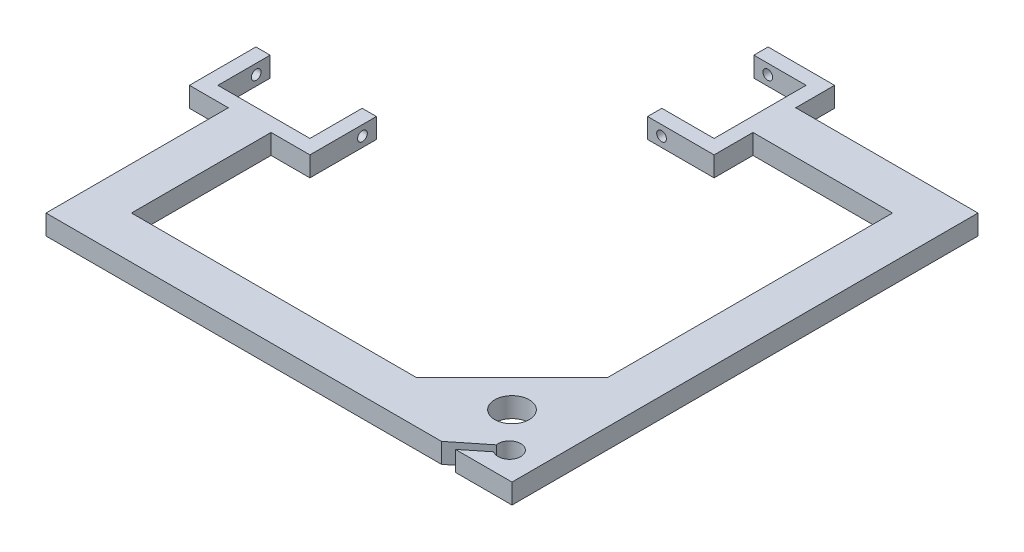
SolidWorks part; units mm, degrees
ref_plane "Front Plane" through (0, 0, 0) normal (0, 0, 1) x (1, 0, 0)
ref_plane "Top Plane" through (0, 0, 0) normal (0, 1, 0) x (1, 0, 0)
ref_plane "Right Plane" through (0, 0, 0) normal (1, 0, 0) x (0, 0, -1)
sketch "Sketch1" plane through (0, 0, 0) normal (0, 1, 0) x (1, 0, 0)
  line L0 (-84.9, -24.6552) -> (-84.9, -42.9952)
  line L1 (-84.9, -42.9952) -> (-52.6, -42.9952)
  line L2 (-52.6, -42.9952) -> (-52.6, -24.6552)
  line L3 (-52.6, -24.6552) -> (-47.6, -24.6552)
  line L4 (-47.6, -24.6552) -> (-47.6, -47.9952)
  line L5 (-47.6, -47.9952) -> (-61.25, -47.9952)
  line L6 (-84.9, -24.6552) -> (-89.9, -24.6552)
  line L7 (-89.9, -24.6552) -> (-89.9, -47.9952)
  line L8 (-89.9, -47.9952) -> (-76.25, -47.9952)
  line L9 (-76.25, -47.9952) -> (-76.25, -111.9952)
  line L10 (-61.25, -47.9952) -> (-61.25, -96.9952)
  line L11 (-76.25, -111.9952) -> (38.75, -111.9952)
  line L12 (-61.25, -96.9952) -> (38.75, -96.9952)
  line L14 (23.34, 36.5948) -> (23.34, 22.9448)
  line L15 (23.34, 22.9448) -> (0, 22.9448)
  line L16 (0, 22.9448) -> (0, 27.9448)
  line L17 (0, 27.9448) -> (18.34, 27.9448)
  line L18 (18.34, 27.9448) -> (18.34, 60.2448)
  line L19 (18.34, 60.2448) -> (0, 60.2448)
  line L20 (0, 60.2448) -> (0, 65.2448)
  line L21 (0, 65.2448) -> (23.34, 65.2448)
  line L22 (23.34, 65.2448) -> (23.34, 51.5948)
  line L28 (23.34, 36.5948) -> (72.34, 36.5948)
  line L29 (72.34, 36.5948) -> (72.34, -63.4052)
  line L30 (23.34, 51.5948) -> (87.34, 51.5948)
  line L31 (87.34, 51.5948) -> (87.34, -63.4052)
  line L32 (72.34, -63.4052) -> (38.75, -96.9952)
  line L34 (87.34, -111.9952) -> (87.34, -63.4052)
  line L35 (73.2655, -103.434) -> (62.5726, -111.9952)
  line L36 (67.475, -111.9952) -> (74.9461, -106.0135)
  line L37 (67.475, -111.9952) -> (87.34, -111.9952)
  line L38 (62.5726, -111.9952) -> (38.75, -111.9952)
  circle A2 centre (65.34, -89.9952) radius 6.05
  arc A3 (74.9461, -106.0135) -> (73.2655, -103.434) centre (77.17, -102.7275) ccw
  dimension "D11" = 7
  dimension "D12" = 7
  dimension "D13" = 12.1
  dimension "D1" = 5
  dimension "D2" = 18.34
  dimension "D3" = 5
  dimension "D4" = 32.3
  dimension "D5" = 100
  dimension "D6" = 15
  dimension "D7" = 49
  dimension "D8" = 15
  dimension "D9" = 70.94
  dimension "D10" = 70.94
  dimension "D14" = 4.9023
extrude "Boss-Extrude1" add sketch "Sketch1" along normal blind 7
sketch "Sketch2" plane through (0, 0, -22.9448) normal (0, 0, 1) x (1, 0, 0)
  line L0 (0, 7) -> (0, 0) construction
  line L1 (0, 7) -> (23.34, 7) construction
  line L3 (0, 0) -> (23.34, 0) construction
  circle A0 centre (4.9, 3.5) radius 1.7
  dimension "D1" = 3.4
  dimension "D2" = 4.9
  dimension "D3" = 3.5
  dimension "D4" = 3.5
extrude "Cut-Extrude1" cut sketch "Sketch2" against normal blind 50
sketch "Sketch3" plane through (-47.6, 0, 0) normal (1, 0, 0) x (0, 0, -1)
  line L0 (-24.6552, 7) -> (-24.6552, 0) construction
  line L1 (-47.9952, 7) -> (-24.6552, 7) construction
  line L2 (-47.9952, 0) -> (-24.6552, 0) construction
  circle A0 centre (-29.5552, 3.5) radius 1.7
  dimension "D1" = 3.4
  dimension "D3" = 3.5
  dimension "D4" = 3.5
  dimension "D2" = 4.9
extrude "Cut-Extrude2" cut sketch "Sketch3" against normal blind 50
